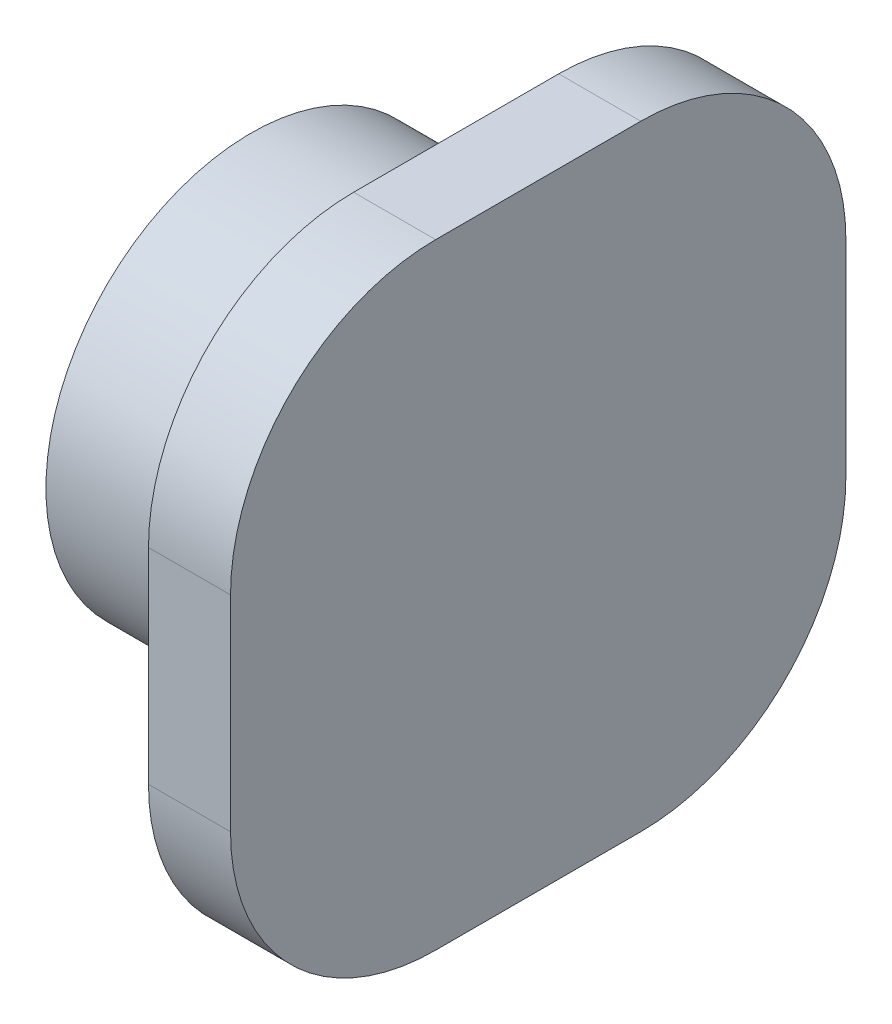
SolidWorks part; units mm, degrees
material "PET"
ref_plane "Front Plane" through (0, 0, 0) normal (0, 0, 1) x (1, 0, 0)
ref_plane "Top Plane" through (0, 0, 0) normal (0, 1, 0) x (1, 0, 0)
ref_plane "Right Plane" through (0, 0, 0) normal (1, 0, 0) x (0, 0, -1)
sketch "Sketch1" plane through (0, 0, 0) normal (1, 0, 0) x (0, 0, -1)
  circle A0 centre (0, 0) radius 9.525
  circle A1 centre (0, 0) radius 12.7
  dimension "D1" = 19.05
  dimension "D2" = 25.4
extrude "Boss-Extrude1" add sketch "Sketch1" along normal blind 12.7
thread "Thread1" start angle 0, offset 0, length 0, pitch 2.54, diameter 19.05
ref_plane "Plane1" through (0, 0, -9.525) normal (0, -1, 0) x (0, 0, -1)
sketch "Thread Profile1" plane through (0, 0, -9.525) normal (0, -1, 0) x (0, 0, -1)
  line L0 (0, 0) -> (0, 2.54) construction
  line L11 (0, 0) -> (0, 2.2225)
  line L12 (0, 2.2225) -> (-1.3748, 1.4287)
  line L13 (-1.3748, 1.4287) -> (-1.3748, 0.7937)
  line L15 (-1.3748, 0.7937) -> (0, 0)
  line L17 (-1.3748, 1.1112) -> (0, 1.1112) construction
  point P2 (0, 0)
  dimension "Pitch" = 2.54
  dimension "Profile_Angle" = 60
  dimension "Profile_Land" = 0.635
  dimension "Profile_Height" = 1.3748
sketch "Sketch4" plane through (12.7, 0, 0) normal (1, 0, 0) x (0, 0, -1)
  line L1 (-6.35, 19.05) -> (6.35, 19.05)
  line L2 (-19.05, 6.35) -> (-19.05, -6.35)
  line L3 (-6.35, -19.05) -> (6.35, -19.05)
  line L4 (19.05, 6.35) -> (19.05, -6.35)
  arc A0 (6.35, -19.05) -> (19.05, -6.35) centre (6.35, -6.35) ccw
  arc A1 (-19.05, -6.35) -> (-6.35, -19.05) centre (-6.35, -6.35) ccw
  arc A2 (-6.35, 19.05) -> (-19.05, 6.35) centre (-6.35, 6.35) ccw
  arc A3 (6.35, 19.05) -> (19.05, 6.35) centre (6.35, 6.35) cw
  point P7 (19.05, -19.05)
  point P12 (-19.05, 19.05)
  point P15 (19.05, 19.05)
  dimension "D5" = 12.7
  dimension "D1" = 38.1
  dimension "D2" = 38.1
  dimension "D3" = 19.05
  dimension "D4" = 19.05
extrude "Boss-Extrude2" add sketch "Sketch4" along normal blind 5.08
